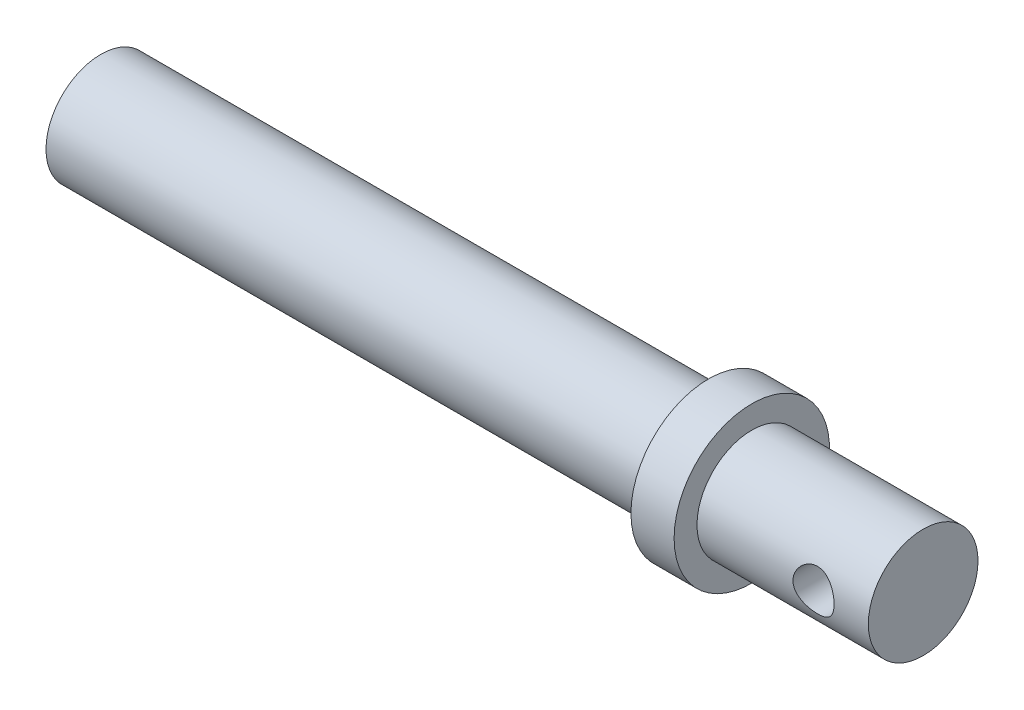
SolidWorks part; units mm, degrees
material "Titanium Ti-8Mn, Annealed"
ref_plane "front" through (0, 0, 0) normal (0, 0, 1) x (1, 0, 0)
ref_plane "top" through (0, 0, 0) normal (0, 1, 0) x (1, 0, 0)
ref_plane "side" through (0, 0, 0) normal (1, 0, 0) x (0, 0, -1)
sketch "Sketch1" plane through (0, 0, 0) normal (1, 0, 0) x (0, 0, -1)
  circle A0 centre (0, 0) radius 6.35
  dimension "D1" = 12.7
extrude "Base-Extrude" add sketch "Sketch1" along normal blind 95.25
sketch "Sketch2" plane through (0, 0, 0) normal (0, 0, 1) x (1, 0, 0)
  line L0 (95.25, 6.35) -> (95.25, -6.35) construction
  line L1 (50, 0) -> (-50, 0) construction
  circle A0 centre (88.9, 0) radius 2.3813
  dimension "D2" = 4.7625
  dimension "D1" = 6.35
extrude "Cut-Extrude1" cut sketch "Sketch2" against normal through all and the other way through all
sketch "Sketch3" plane through (0, 0, 0) normal (-1, 0, 0) x (0, 0, 1)
  circle A0 centre (0, 0) radius 2.3813
  dimension "D1" = 4.7625
extrude "Cut-Extrude2" cut sketch "Sketch3" against normal blind 25.4
ref_axis "Axis1" through (145.25, 0, 0) along (-1, 0, 0)
ref_plane "Plane1" through (70.4, 0, 0) normal (-1, 0, 0) x (0, 0, 1)
sketch "Sketch4" plane through (70.4, 0, 0) normal (-1, 0, 0) x (0, 0, 1)
  circle A0 centre (0, 0) radius 9
  dimension "D1" = 18
extrude "Extrude1" add sketch "Sketch4" against normal blind 5
